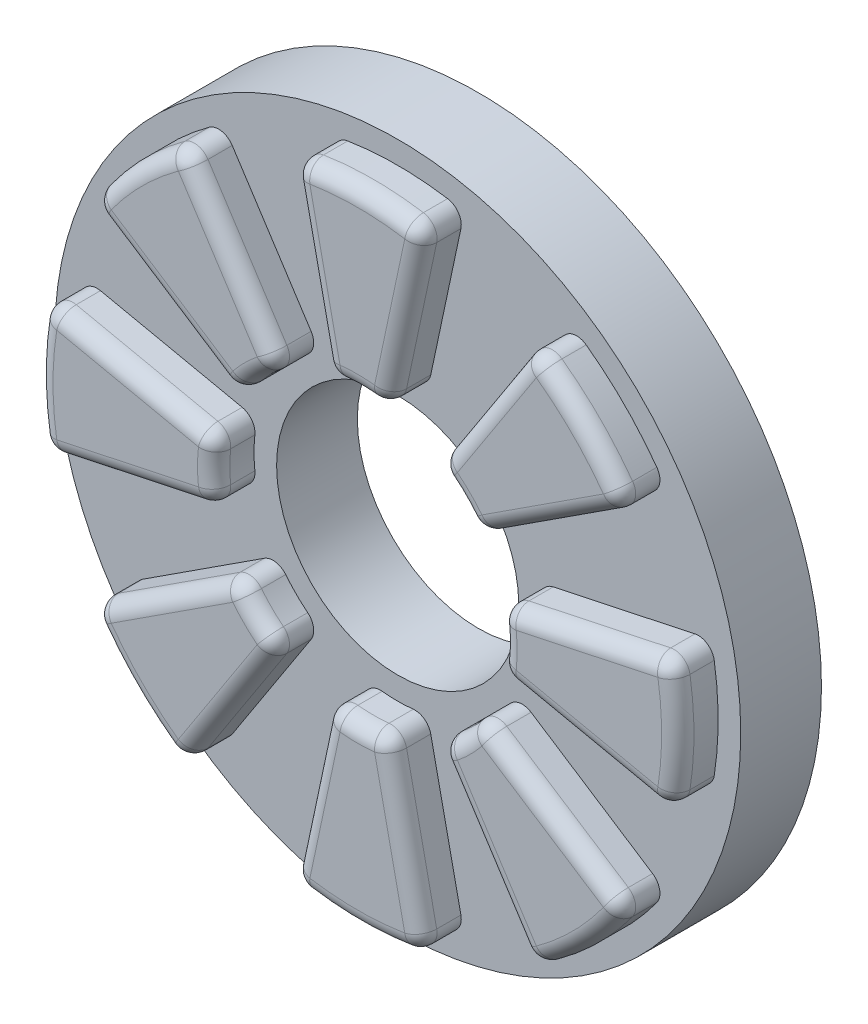
SolidWorks part; units mm, degrees
ref_plane "Front Plane" through (0, 0, 0) normal (0, 0, 1) x (1, 0, 0)
ref_plane "Top Plane" through (0, 0, 0) normal (0, 1, 0) x (1, 0, 0)
ref_plane "Right Plane" through (0, 0, 0) normal (1, 0, 0) x (0, 0, -1)
sketch "Sketch1" plane through (0, 0, 0) normal (0, 0, 1) x (1, 0, 0)
  circle A0 centre (0, 0) radius 26.9875
  circle A1 centre (0, 0) radius 9.525
  dimension "D1" = 53.975
  dimension "D2" = 19.05
extrude "Boss-Extrude1" add sketch "Sketch1" along normal blind 6.35
sketch "Sketch3" plane through (0, 0, 6.35) normal (0, 0, 1) x (1, 0, 0)
  line L0 (-5.2453, 24.6578) -> (-2.3518, 11.0556)
  line L1 (2.3518, 11.0556) -> (5.2453, 24.6578)
  line L2 (-7.8152, 24.1111) -> (-2.6753, 25.2045) construction
  line L3 (9.4805, 6.1546) -> (21.1446, 13.7267)
  line L4 (13.7267, 21.1446) -> (6.1546, 9.4805)
  line L5 (11.0556, -2.3518) -> (24.6578, -5.2453)
  line L6 (24.6578, 5.2453) -> (11.0556, 2.3518)
  line L7 (6.1546, -9.4805) -> (13.7267, -21.1446)
  line L8 (21.1446, -13.7267) -> (9.4805, -6.1546)
  line L9 (-2.3518, -11.0556) -> (-5.2453, -24.6578)
  line L10 (5.2453, -24.6578) -> (2.3518, -11.0556)
  line L11 (-9.4805, -6.1546) -> (-21.1446, -13.7267)
  line L12 (-13.7267, -21.1446) -> (-6.1546, -9.4805)
  line L13 (-11.0556, 2.3518) -> (-24.6578, 5.2453)
  line L14 (-24.6578, -5.2453) -> (-11.0556, -2.3518)
  line L15 (-6.1546, 9.4805) -> (-13.7267, 21.1446)
  line L16 (-21.1446, 13.7267) -> (-9.4805, 6.1546)
  circle A0 centre (0, 0) radius 25.2095 construction
  circle A1 centre (0, 0) radius 11.303 construction
  arc A2 (-2.3518, 11.0556) -> (2.3518, 11.0556) centre (0, 0) cw
  circle A4 centre (0, 0) radius 9.525 construction
  arc A5 (-5.2453, 24.6578) -> (5.2453, 24.6578) centre (0, 0) cw
  arc A6 (13.7267, 21.1446) -> (21.1446, 13.7267) centre (0, 0) cw
  arc A7 (6.1546, 9.4805) -> (9.4805, 6.1546) centre (0, 0) cw
  arc A8 (24.6578, 5.2453) -> (24.6578, -5.2453) centre (0, 0) cw
  arc A9 (11.0556, 2.3518) -> (11.0556, -2.3518) centre (0, 0) cw
  arc A10 (21.1446, -13.7267) -> (13.7267, -21.1446) centre (0, 0) cw
  arc A11 (9.4805, -6.1546) -> (6.1546, -9.4805) centre (0, 0) cw
  arc A12 (5.2453, -24.6578) -> (-5.2453, -24.6578) centre (0, 0) cw
  arc A13 (2.3518, -11.0556) -> (-2.3518, -11.0556) centre (0, 0) cw
  arc A14 (-13.7267, -21.1446) -> (-21.1446, -13.7267) centre (0, 0) cw
  arc A15 (-6.1546, -9.4805) -> (-9.4805, -6.1546) centre (0, 0) cw
  arc A16 (-24.6578, -5.2453) -> (-24.6578, 5.2453) centre (0, 0) cw
  arc A17 (-11.0556, -2.3518) -> (-11.0556, 2.3518) centre (0, 0) cw
  arc A18 (-21.1446, 13.7267) -> (-13.7267, 21.1446) centre (0, 0) cw
  arc A19 (-9.4805, 6.1546) -> (-6.1546, 9.4805) centre (0, 0) cw
  circle A20 centre (0, 0) radius 26.9875 construction
  point P5 (0, 11.303)
  point P8 (0, 25.2095)
  point P9 (0, 11.303)
  point P21 (-5.2453, 24.6578)
  dimension "D1" = 1.778
  dimension "D2" = 1.778
  dimension "D3" = 8
extrude "Boss-Extrude2" add sketch "Sketch3" along normal blind 3.175
fillet "Fillet1" radius 1.27 32 edges at (-24.6578, 5.2453, 7.9375) (21.1446, -13.7267, 7.9375) (24.6578, 5.2453, 7.9375) (9.4805, -6.1546, 7.9375) (2.3518, -11.0556, 7.9375) (-6.1546, -9.4805, 7.9375) (-9.4805, -6.1546, 7.9375) (-11.0556, 2.3518, 7.9375) (11.0556, -2.3518, 7.9375) (24.6578, -5.2453, 7.9375) (5.2453, -24.6578, 7.9375) (-24.6578, -5.2453, 7.9375) (-11.0556, -2.3518, 7.9375) (-21.1446, -13.7267, 7.9375) (-13.7267, -21.1446, 7.9375) (-2.3518, -11.0556, 7.9375) (-5.2453, -24.6578, 7.9375) (13.7267, -21.1446, 7.9375) (6.1546, -9.4805, 7.9375) (9.4805, 6.1546, 7.9375) (11.0556, 2.3518, 7.9375) (6.1546, 9.4805, 7.9375) (21.1446, 13.7267, 7.9375) (13.7267, 21.1446, 7.9375) (-5.2453, 24.6578, 7.9375) (5.2453, 24.6578, 7.9375) (2.3518, 11.0556, 7.9375) (-2.3518, 11.0556, 7.9375) (-9.4805, 6.1546, 7.9375) (-6.1546, 9.4805, 7.9375) (-13.7267, 21.1446, 7.9375) (-21.1446, 13.7267, 7.9375)
fillet "Fillet2" radius 1.27 64 edges at (-4.7783, -24.3664, 9.525) (-3.7883, -17.8088, 9.525) (-2.1049, -11.4703, 9.525) (0, -11.303, 9.525) (2.1049, -11.4703, 9.525) (3.7883, -17.8088, 9.525) (4.7783, -24.3664, 9.525) (0, -25.2095, 9.525) (-13.8509, -20.6084, 9.525) (-17.8258, -17.8258, 9.525) (-20.6084, -13.8509, 9.525) (-15.2714, -9.914, 9.525) (-9.5991, -6.6223, 9.525) (-7.9924, -7.9924, 9.525) (-6.6223, -9.5991, 9.525) (13.8509, -20.6084, 9.525) (9.914, -15.2714, 9.525) (6.6223, -9.5991, 9.525) (7.9924, -7.9924, 9.525) (9.5991, -6.6223, 9.525) (15.2714, -9.914, 9.525) (20.6084, -13.8509, 9.525) (17.8258, -17.8258, 9.525) (24.3664, -4.7783, 9.525) (17.8088, -3.7883, 9.525) (11.4703, -2.1049, 9.525) (11.303, 0, 9.525) (11.4703, 2.1049, 9.525) (17.8088, 3.7883, 9.525) (24.3664, 4.7783, 9.525) (25.2095, 0, 9.525) (6.6223, 9.5991, 9.525) (9.914, 15.2714, 9.525) (13.8509, 20.6084, 9.525) (17.8258, 17.8258, 9.525) (20.6084, 13.8509, 9.525) (15.2714, 9.914, 9.525) (9.5991, 6.6223, 9.525) (7.9924, 7.9924, 9.525) (4.7783, 24.3664, 9.525) (3.7883, 17.8088, 9.525) (2.1049, 11.4703, 9.525) (0, 11.303, 9.525) (-2.1049, 11.4703, 9.525) (-3.7883, 17.8088, 9.525) (-4.7783, 24.3664, 9.525) (0, 25.2095, 9.525) (-20.6084, 13.8509, 9.525) (-17.8258, 17.8258, 9.525) (-13.8509, 20.6084, 9.525) (-9.914, 15.2714, 9.525) (-6.6223, 9.5991, 9.525) (-7.9924, 7.9924, 9.525) (-9.5991, 6.6223, 9.525) (-15.2714, 9.914, 9.525) (-11.4703, 2.1049, 9.525) (-11.303, 0, 9.525) (-11.4703, -2.1049, 9.525) (-17.8088, -3.7883, 9.525) (-24.3664, -4.7783, 9.525) (-25.2095, 0, 9.525) (-24.3664, 4.7783, 9.525) (-17.8088, 3.7883, 9.525) (-9.914, -15.2714, 9.525)
equation "\"D1@Chamfer1\"=1/8"
